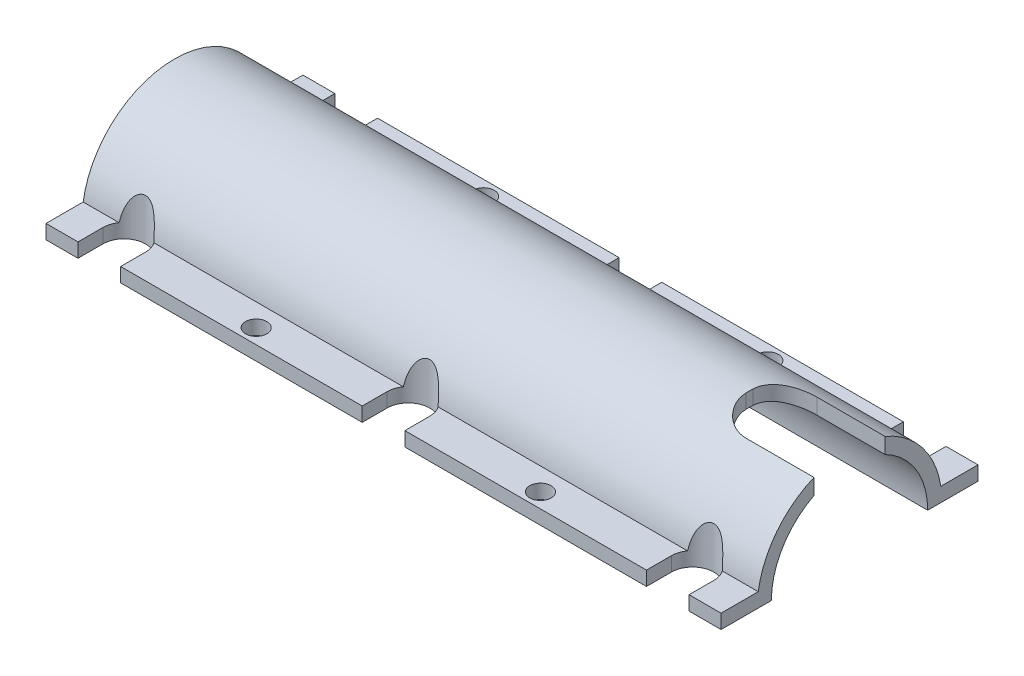
SolidWorks part; units mm, degrees
ref_plane "Спереди" through (0, 0, 0) normal (0, 0, 1) x (1, 0, 0)
ref_plane "Сверху" through (0, 0, 0) normal (0, 1, 0) x (1, 0, 0)
ref_plane "Справа" through (0, 0, 0) normal (1, 0, 0) x (0, 0, -1)
sketch "Эскиз1" plane through (0, 0, 0) normal (1, 0, 0) x (0, 0, -1)
  line L0 (11, 0) -> (18.0795, 0)
  line L1 (18.0795, 0) -> (18.0795, 2)
  line L2 (18.0795, 2) -> (12.8481, 2)
  line L3 (0, 0) -> (0, 11) construction
  line L4 (-18.0795, 2) -> (-12.848, 2.0004)
  line L5 (-18.0795, 0) -> (-18.0795, 2)
  line L6 (-11, 0) -> (-18.0795, 0)
  arc A0 (-11, 0) -> (11, 0) centre (0, 0) cw
  arc A4 (-12.848, 2.0004) -> (12.8481, 2) centre (0, 0) cw
extrude "Бобышка-Вытянуть1" add sketch "Эскиз1" along normal blind 95
sketch "Эскиз2" plane through (0, 2.0015, 0.0002) normal (0, 1, 0.0001) x (1, 0, 0)
  line L0 (0, -18.0793) -> (0, -14.5793) construction
  line L1 (4.5, -14.5793) -> (4.5, -18.2988)
  line L2 (0, -12.8479) -> (0, -18.0793) construction
  line L5 (0, -14.5793) -> (7.5, -14.5793) construction
  line L6 (4.5, -18.2988) -> (10.5, -18.2988)
  line L32 (10.5, -18.2988) -> (10.5, -14.5793)
  line L33 (50.5, -18.2988) -> (50.5, -14.5793)
  line L34 (44.5, -14.5793) -> (44.5, -18.2988)
  line L35 (44.5, -18.2988) -> (50.5, -18.2988)
  line L36 (90.5, -18.2988) -> (90.5, -14.5793)
  line L37 (84.5, -14.5793) -> (84.5, -18.2988)
  line L38 (84.5, -18.2988) -> (90.5, -18.2988)
  line L39 (84.5, 18.2988) -> (90.5, 18.2988)
  line L40 (84.5, 14.5793) -> (84.5, 18.2988)
  line L41 (90.5, 18.2988) -> (90.5, 14.5793)
  line L42 (44.5, 18.2988) -> (50.5, 18.2988)
  line L43 (44.5, 14.5793) -> (44.5, 18.2988)
  line L44 (50.5, 18.2988) -> (50.5, 14.5793)
  line L45 (4.5, 18.2988) -> (10.5, 18.2988)
  line L46 (4.5, 14.5793) -> (4.5, 18.2988)
  line L47 (10.5, 18.2988) -> (10.5, 14.5793)
  circle A0 centre (27.5, -16) radius 1.5
  circle A1 centre (67.5, -16) radius 1.5
  circle A2 centre (67.5, 16) radius 1.5
  circle A3 centre (27.5, 16) radius 1.5
  arc A10 (10.5, -14.5793) -> (4.5, -14.5793) centre (7.5, -14.5793) ccw
  arc A11 (50.5, -14.5793) -> (44.5, -14.5793) centre (47.5, -14.5793) ccw
  arc A12 (90.5, -14.5793) -> (84.5, -14.5793) centre (87.5, -14.5793) ccw
  arc A13 (90.5, 14.5793) -> (84.5, 14.5793) centre (87.5, 14.5793) cw
  arc A14 (50.5, 14.5793) -> (44.5, 14.5793) centre (47.5, 14.5793) cw
  arc A15 (10.5, 14.5793) -> (4.5, 14.5793) centre (7.5, 14.5793) cw
  dimension "D1" = 2
  dimension "D2" = 3
extrude "Вырез-Вытянуть1" cut sketch "Эскиз2" against normal through all and the other way through all
sketch "Эскиз3" plane through (0, 0, 0) normal (0, -1, 0) x (1, 0, 0)
  line L0 (0, 0) -> (95, 0) construction
  line L1 (95, -11) -> (95, 11) construction
  line L3 (85.4096, 5) -> (95, 5)
  line L4 (80.9096, 0.5) -> (80.9096, -0.5)
  line L5 (85.4096, -5) -> (95, -5)
  line L6 (95, 5) -> (95, -5)
  line L7 (80.9096, 5) -> (95, -5) construction
  line L8 (80.9096, -5) -> (95, 5) construction
  arc A0 (80.9096, 0.5) -> (85.4096, 5) centre (85.4096, 0.5) cw
  arc A1 (80.9096, -0.5) -> (85.4096, -5) centre (85.4096, -0.5) ccw
  point P5 (87.9548, 0)
  dimension "D1" = 4.5
  dimension "D2" = 4.5
extrude "Вырез-Вытянуть2" cut sketch "Эскиз3" against normal through all
